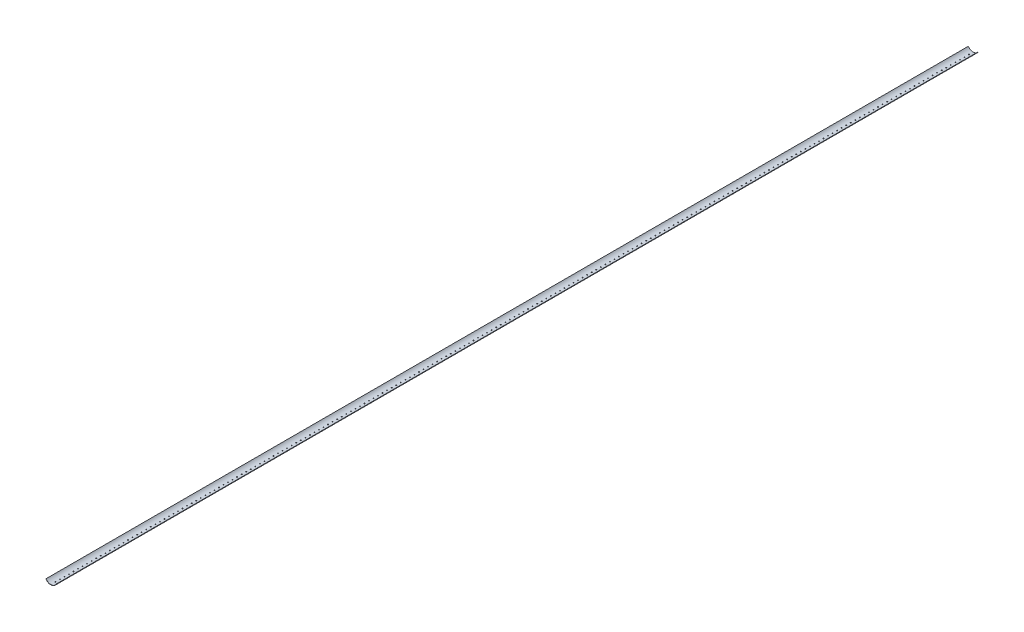
SolidWorks part; units mm, degrees
ref_plane "Front Plane" through (0, 0, 0) normal (0, 0, 1) x (1, 0, 0)
ref_plane "Top Plane" through (0, 0, 0) normal (0, 1, 0) x (1, 0, 0)
ref_plane "Right Plane" through (0, 0, 0) normal (1, 0, 0) x (0, 0, -1)
sketch "Sketch2" plane through (0, 0, 0) normal (0, 0, 1) x (1, 0, 0)
  line L0 (14.445, 7.82) -> (14.445, 6.82)
  line L5 (0, 0) -> (28.89, 0)
  line L6 (0, 0) -> (0, 7.82)
  line L7 (0, 7.82) -> (28.89, 7.82)
  line L8 (28.89, 0) -> (28.89, 7.82)
  line L9 (0, 0) -> (28.89, 0)
  line L10 (0, 0) -> (0, -1)
  line L11 (0, -1) -> (28.89, -1)
  line L12 (28.89, 0) -> (28.89, -1)
  spline S0 degree 2 poles (0, 0) (14.445, 15.64) (28.89, 0) knots 0 0 0 1 1 1
  spline S1 degree 2 poles (0, -1) (14.445, 14.64) (28.89, -1) knots 0 0 0 1 1 1
  dimension "D4" = 33.8133
  dimension "D1" = 7.82
  dimension "D2" = 28.89
sketch "Sketch3" plane through (0, 0, 0) normal (0, 0, 1) x (1, 0, 0)
  line L0 (28.89, 0.001) -> (28.89, 0.9945)
  line L1 (0, 0.001) -> (0, 0.9945)
  arc A0 (0, 0.001) -> (28.89, 0.001) centre (14.445, 9.4482) ccw
  arc A1 (0, 0.9945) -> (28.89, 0.9945) centre (14.445, 10.4482) ccw
  dimension "D1" = 17.26
extrude "Boss-Extrude3" add sketch "Sketch3" along normal blind 2743.2 contours A0 L0 A1 L1
ref_axis "Axis1" through (14.445, 10.4482, 2743.2) along (0, 0, -1)
sketch "Sketch5" plane through (0, 0, 0) normal (0, 1, 0) x (1, 0, 0)
  circle A0 centre (14.445, -12.3378) radius 1.25
  dimension "D1" = 2.5
extrude "Cut-Extrude1" cut sketch "Sketch5" against normal blind 10
pattern_linear "LPattern2" count 203 spacing 13.52 along (0, 0, 1) of "Cut-Extrude1"
